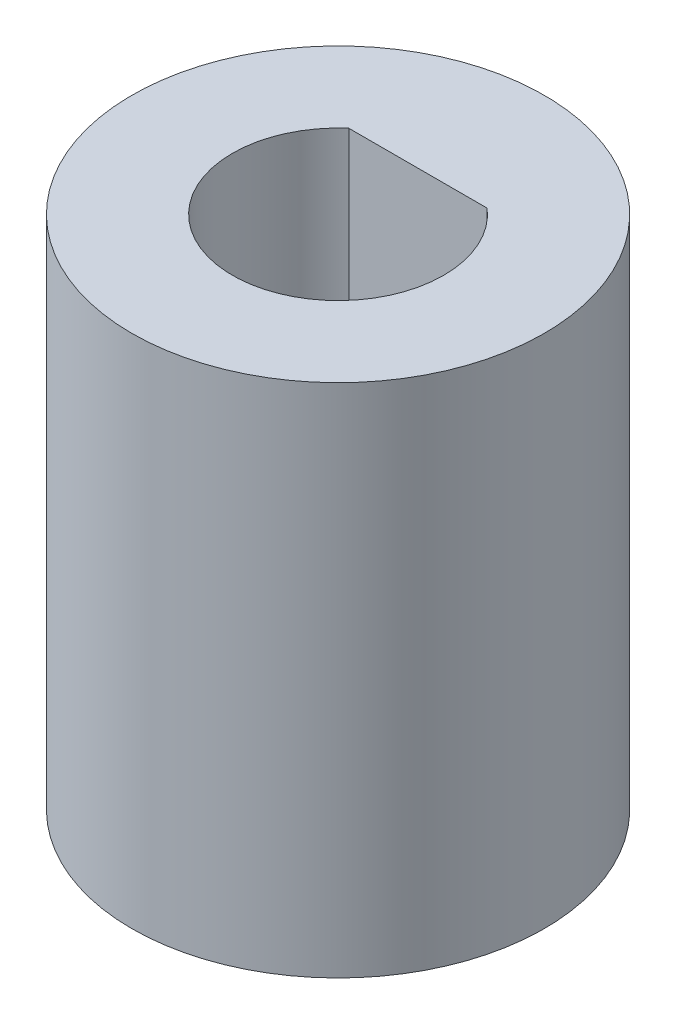
SolidWorks part; units mm, degrees
ref_plane "Front Plane" through (0, 0, 0) normal (0, 0, 1) x (1, 0, 0)
ref_plane "Top Plane" through (0, 0, 0) normal (0, 1, 0) x (1, 0, 0)
ref_plane "Right Plane" through (0, 0, 0) normal (1, 0, 0) x (0, 0, -1)
sketch "Sketch1" plane through (0, 0, 0) normal (0, 1, 0) x (1, 0, 0)
  line L0 (-1.3416, 1.55) -> (1.3416, 1.55)
  circle A0 centre (0, 0) radius 4
  circle A1 centre (0, 0) radius 2.05
  dimension "D1" = 8
  dimension "D2" = 4.1
  dimension "D3" = 0.5
extrude "Boss-Extrude1" add sketch "Sketch1" along normal blind 10 contours A0 A1 | L0 A1 region at (0, 0, -1.7523) region at (-3.8869, 0, 0)
